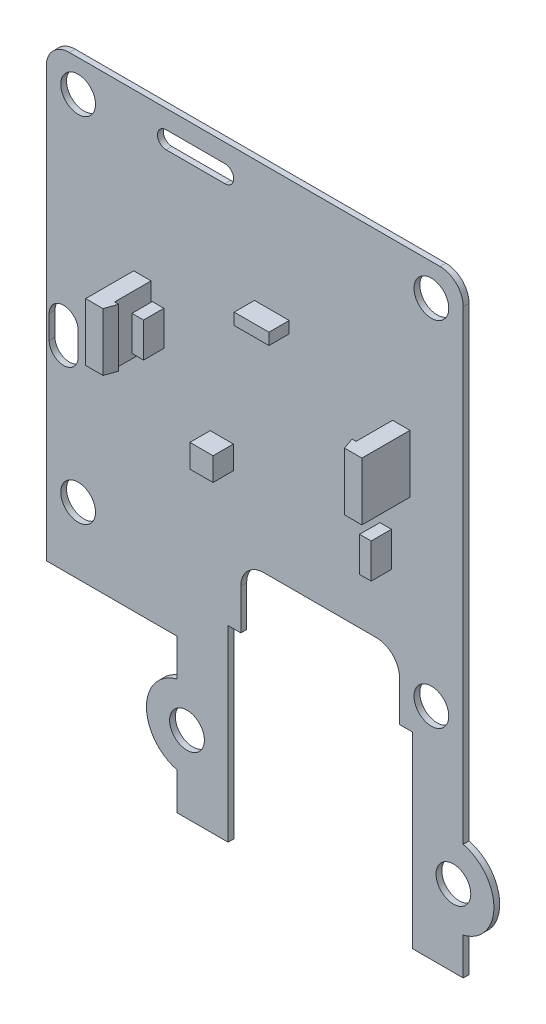
SolidWorks part; units mm, degrees
ref_plane "Front Plane" through (0, 0, 0) normal (0, 0, 1) x (1, 0, 0)
ref_plane "Top Plane" through (0, 0, 0) normal (0, 1, 0) x (1, 0, 0)
ref_plane "Right Plane" through (0, 0, 0) normal (1, 0, 0) x (0, 0, -1)
sketch "Sketch1" plane through (0, 0, 0) normal (0, 0, 1) x (1, 0, 0)
  line L0 (-17.75, -2.4) -> (-17.75, -4.4) construction
  line L1 (-15.25, -2.4) -> (-15.25, -4.4) construction
  line L2 (-17.75, -2.4) -> (-17.75, -4.4)
  line L3 (-15.25, -2.4) -> (-15.25, -4.4)
  line L4 (-7.65, 14.9) -> (-2.57, 14.9) construction
  line L5 (13.6, -18.1) -> (13.6, -34.2)
  line L6 (13.6, -34.2) -> (18, -34.2)
  line L7 (-2.3, -34.2) -> (-2.3, -18.1)
  line L8 (16, 18) -> (-16, 18)
  line L9 (-18, 16) -> (-18, -18)
  line L10 (-18, -18) -> (-1.2, -18)
  line L11 (-1.2, -18) -> (-1.2, -14.5)
  line L12 (0.8, -12.5) -> (10.5, -12.5)
  line L13 (12.5, -14.5) -> (12.5, -18)
  line L14 (12.5, -18) -> (18, -18)
  line L15 (18, -18) -> (18, 16)
  line L16 (16, 18) -> (-16, 18)
  line L17 (-18, 16) -> (-18, -18)
  line L18 (-18, -18) -> (-1.2, -18)
  line L19 (-1.2, -18) -> (-1.2, -14.5)
  line L20 (0.8, -12.5) -> (10.5, -12.5)
  line L21 (12.5, -14.5) -> (12.5, -18)
  line L22 (12.5, -18) -> (18, -18)
  line L23 (18, -18) -> (18, 16)
  line L24 (-2.3, -18.1) -> (-18, -18.1)
  line L25 (-18, -18.1) -> (-18, -21)
  line L26 (-18, -21) -> (-6.7, -21)
  line L27 (-6.7, -21) -> (-6.7, -24.2048)
  line L28 (-6.7, -30.9952) -> (-6.7, -34.2)
  line L29 (-6.7, -34.2) -> (-2.3, -34.2)
  line L30 (-2.3, -34.2) -> (-2.3, -18.1)
  line L31 (-2.3, -18.1) -> (-18, -18.1)
  line L32 (-18, -18.1) -> (-18, -21)
  line L33 (-18, -21) -> (-6.7, -21)
  line L34 (-6.7, -21) -> (-6.7, -24.2048)
  line L35 (-6.7, -30.9952) -> (-6.7, -34.2)
  line L36 (-6.7, -34.2) -> (-2.3, -34.2)
  line L37 (18, -34.2) -> (18, -30.9952)
  line L38 (18, -24.2048) -> (18, -18.1)
  line L39 (18, -18.1) -> (13.6, -18.1)
  line L40 (13.6, -18.1) -> (13.6, -34.2)
  line L41 (13.6, -34.2) -> (18, -34.2)
  line L42 (18, -34.2) -> (18, -30.9952)
  line L43 (18, -24.2048) -> (18, -18.1)
  line L44 (18, -18.1) -> (13.6, -18.1)
  line L45 (-7.65, 16.4) -> (-2.57, 16.4) construction
  line L46 (-7.65, 14.9) -> (-2.57, 14.9)
  line L47 (-7.65, 16.4) -> (-2.57, 16.4)
  line L48 (-18, -18) -> (-18, -18.1)
  line L49 (18, -18) -> (18, -18.1)
  line L50 (13.6, -18.1) -> (13.6, -18)
  line L51 (-2.3, -18.1) -> (-2.3, -18)
  arc A0 (-17.75, -4.4) -> (-15.25, -4.4) centre (-16.5, -4.4) ccw construction
  arc A1 (-6.7, -24.2048) -> (-6.7, -30.9952) centre (-5.85, -27.6) ccw
  arc A2 (-6.7, -24.2048) -> (-6.7, -30.9952) centre (-5.85, -27.6) ccw
  arc A3 (18, -30.9952) -> (18, -24.2048) centre (17.15, -27.6) ccw
  arc A4 (-16, 18) -> (-18, 16) centre (-16, 16) ccw
  arc A5 (0.8, -12.5) -> (-1.2, -14.5) centre (0.8, -14.5) ccw
  arc A6 (12.5, -14.5) -> (10.5, -12.5) centre (10.5, -14.5) ccw
  arc A7 (18, 16) -> (16, 18) centre (16, 16) ccw
  arc A8 (-16, 18) -> (-18, 16) centre (-16, 16) ccw
  arc A9 (0.8, -12.5) -> (-1.2, -14.5) centre (0.8, -14.5) ccw
  arc A10 (12.5, -14.5) -> (10.5, -12.5) centre (10.5, -14.5) ccw
  arc A11 (18, 16) -> (16, 18) centre (16, 16) ccw
  arc A12 (18, -30.9952) -> (18, -24.2048) centre (17.15, -27.6) ccw
  arc A13 (-15.25, -2.4) -> (-17.75, -2.4) centre (-16.5, -2.4) ccw construction
  arc A14 (-17.75, -4.4) -> (-15.25, -4.4) centre (-16.5, -4.4) ccw
  arc A15 (-15.25, -2.4) -> (-17.75, -2.4) centre (-16.5, -2.4) ccw
  circle A16 centre (15.25, 15.25) radius 1.5 construction
  circle A17 centre (15.25, -15.25) radius 1.5 construction
  circle A18 centre (17.15, -27.6) radius 1.5 construction
  circle A19 centre (-5.85, -27.6) radius 1.5 construction
  circle A20 centre (-15.25, -15.25) radius 1.5 construction
  circle A21 centre (-15.25, 15.25) radius 1.5 construction
  circle A22 centre (15.25, 15.25) radius 1.5
  circle A23 centre (15.25, -15.25) radius 1.5
  circle A24 centre (17.15, -27.6) radius 1.5
  circle A25 centre (-5.85, -27.6) radius 1.5
  circle A26 centre (-15.25, -15.25) radius 1.5
  circle A27 centre (-15.25, 15.25) radius 1.5
  arc A28 (-2.57, 14.9) -> (-2.57, 16.4) centre (-2.57, 15.65) ccw construction
  arc A29 (-7.65, 16.4) -> (-7.65, 14.9) centre (-7.65, 15.65) ccw construction
  arc A30 (-2.57, 14.9) -> (-2.57, 16.4) centre (-2.57, 15.65) ccw
  arc A31 (-7.65, 16.4) -> (-7.65, 14.9) centre (-7.65, 15.65) ccw
  dimension "D1" = 0
  dimension "D2" = 0
  dimension "D3" = 0
extrude "Base shape" add sketch "Sketch1" along normal blind 0.5 contours L23 A11 L16 A8 L17 L18 L19 A9 L20 A10 L21 L22 A31 L47 A30 L46 A27 A26 A23 A22 A15 L3 A14 L2 | L31 L51 L18 L48 | L34 A2 L35 L36 L30 L31 L32 L33 A25 | L50 L44 L49 L22 | L42 A12 L43 L44 L40 L41 A24 region at (16.2483, -26.2681, 0) region at (15.8, -18.05, 0) region at (-0.1744, 0.8384, 0) region at (-10.15, -18.05, 0) region at (-10.15, -18.3249, 0)
sketch "Sketch2" plane through (0, 0, 0.5) normal (0, 0, 1) x (1, 0, 0)
  line L0 (1.475, 16.95) -> (1.475, -13.05) construction
  line L1 (-7.85, 1.45) -> (-8.85, 1.45) construction
  line L2 (-0.025, 7.45) -> (2.975, 7.45)
  line L3 (-0.025, 7.45) -> (-0.025, 6.45)
  line L4 (11.8, 16.95) -> (-8.85, 16.95)
  line L5 (-8.85, 16.95) -> (-8.85, -13.05)
  line L6 (-8.85, -13.05) -> (11.8, -13.05)
  line L7 (11.8, -13.05) -> (11.8, 16.95)
  line L8 (11.8, 16.95) -> (-8.85, 16.95)
  line L9 (-8.85, 16.95) -> (-8.85, -13.05)
  line L10 (-8.85, -13.05) -> (11.8, -13.05)
  line L11 (11.8, -13.05) -> (11.8, 16.95)
  line L12 (-0.025, 6.45) -> (2.975, 6.45)
  line L13 (2.975, 7.45) -> (2.975, 6.45)
  line L14 (-0.025, 7.45) -> (2.975, 6.45) construction
  line L15 (-0.025, 6.45) -> (2.975, 7.45) construction
  line L16 (-8.85, 2.95) -> (-7.85, 2.95)
  line L17 (-8.85, 2.95) -> (-8.85, -0.05)
  line L18 (-8.85, -0.05) -> (-7.85, -0.05)
  line L19 (-7.85, 2.95) -> (-7.85, -0.05)
  line L20 (-3.85, -4.2) -> (-1.85, -4.2)
  line L21 (-3.85, -4.2) -> (-3.85, -6.2)
  line L22 (-3.85, -6.2) -> (-1.85, -6.2)
  line L23 (-1.85, -4.2) -> (-1.85, -6.2)
  line L24 (11.8, -3.75) -> (10.8, -3.75)
  line L25 (11.8, -3.75) -> (11.8, -6.75)
  line L26 (11.8, -6.75) -> (10.8, -6.75)
  line L27 (10.8, -3.75) -> (10.8, -6.75)
  line L28 (11.8, 1.95) -> (10.8, 1.95)
  line L29 (11.8, 1.95) -> (11.8, -1.05)
  line L30 (11.8, -1.05) -> (10.8, -1.05)
  line L31 (10.8, 1.95) -> (10.8, -1.05)
  line L32 (-3.85, -5.2) -> (-1.85, -5.2) construction
  line L33 (-2.85, -4.2) -> (-2.85, -6.2) construction
  line L34 (10.8, 0.45) -> (11.8, 0.45) construction
  line L35 (10.8, -5.25) -> (11.8, -5.25) construction
  point P6 (1.475, 6.95)
  dimension "D2" = 3
  dimension "D3" = 1
  dimension "D4" = 10
  dimension "D5" = 7.8
  dimension "D6" = 16.5
  dimension "D7" = 7.85
  dimension "D8" = 6
  dimension "D9" = 2
  dimension "D10" = 15.5
  dimension "D1" = 0
extrude "RX supports" add sketch "Sketch2" along normal blind 1.75 contours L13 L2 L3 L12 | L19 L16 L9 L18 | L23 L20 L21 L22 | L28 L31 L30 L11 | L24 L27 L26 L11 region at (1.475, 6.95, 0.5) region at (11.3, 0.45, 0.5) region at (-8.35, 1.45, 0.5) region at (11.3, -5.25, 0.5) region at (-2.85, -5.2, 0.5)
sketch "Sketch3" plane through (0, 0, 0.5) normal (0, 0, 1) x (1, 0, 0)
  line L0 (-8.85, 1.95) -> (11.8, 1.95) construction
  line L1 (1.475, 16.95) -> (1.475, -13.05) construction
  line L2 (-8.95, 4.45) -> (-10.45, 4.45)
  line L3 (-8.95, 4.45) -> (-8.95, -0.55)
  line L4 (11.8, 16.95) -> (-8.85, 16.95)
  line L5 (-8.85, 16.95) -> (-8.85, -13.05)
  line L6 (-8.85, -13.05) -> (11.8, -13.05)
  line L7 (11.8, -13.05) -> (11.8, 16.95)
  line L8 (11.8, 16.95) -> (-8.85, 16.95)
  line L9 (-8.85, 16.95) -> (-8.85, -13.05)
  line L10 (-8.85, -13.05) -> (11.8, -13.05)
  line L11 (11.8, -13.05) -> (11.8, 16.95)
  line L12 (-8.95, -0.55) -> (-10.45, -0.55)
  line L13 (-10.45, 4.45) -> (-10.45, -0.55)
  line L14 (11.9, -0.55) -> (13.4, -0.55)
  line L15 (13.4, 4.45) -> (13.4, -0.55)
  line L16 (11.9, 4.45) -> (13.4, 4.45)
  line L17 (11.9, 4.45) -> (11.9, -0.55)
  point P10 (-10.45, 1.95)
  point P13 (0, 0)
  point P14 (0, 0)
  point P15 (-9.1855, 4.45)
  dimension "D2" = 5
  dimension "D3" = 1.5
  dimension "D4" = 0.1
  dimension "D1" = 0
extrude "Clip base" add sketch "Sketch3" along normal offset from surface (3.15 mm away) 0.2 contours L2 L13 L12 L3 | L16 L17 L14 L15 region at (-9.7, 1.95, 0.5) region at (12.65, 1.95, 0.5) offset beyond the face yes
sketch "Sketch4" plane through (0, 0, 3.65) normal (0, 0, 1) x (1, 0, 0)
  line L0 (-8.95, -0.55) -> (-10.45, -0.55) construction
  line L1 (-10.45, 4.45) -> (-8.6, 4.45)
  line L2 (-10.45, 4.45) -> (-10.45, -0.55)
  line L3 (-10.45, -0.55) -> (-8.6, -0.55)
  line L4 (-8.6, 4.45) -> (-8.6, -0.55)
  line L5 (-8.95, 4.45) -> (-8.95, -0.55) construction
  line L6 (-10.45, 1.95) -> (13.4, 1.95) construction
  line L7 (13.4, 4.45) -> (13.4, -0.55) construction
  line L8 (1.475, 4.45) -> (1.475, -0.55) construction
  line L9 (11.55, 4.45) -> (11.55, -0.55)
  line L10 (13.4, 4.45) -> (11.55, 4.45)
  line L11 (13.4, 4.45) -> (13.4, -0.55)
  line L12 (13.4, -0.55) -> (11.55, -0.55)
  point P15 (0, 0)
  point P16 (0, 0)
  point P17 (1.475, 1.95)
  dimension "D1" = 0.35
extrude "Clip top" add sketch "Sketch4" along normal blind 1
sketch "Sketch5" plane through (0, -0.55, 0) normal (0, -1, 0) x (1, 0, 0)
  line L0 (-8.6, 3.65) -> (-8.95, 4.65)
  line L1 (-10.45, 4.65) -> (-8.6, 4.65) construction
  line L2 (-8.95, 4.65) -> (-8.6, 4.65)
  line L3 (-8.6, 4.65) -> (-8.6, 3.65)
  line L4 (-8.95, 3.65) -> (-8.95, 0.5) construction
  line L5 (11.55, 3.65) -> (11.9, 4.65)
  line L6 (11.55, 4.65) -> (13.4, 4.65) construction
  line L7 (11.9, 4.65) -> (11.55, 4.65)
  line L8 (11.55, 4.65) -> (11.55, 3.65)
  line L9 (11.9, 3.65) -> (11.9, 0.5) construction
  point P5 (0, 0)
extrude "Clip chamfer" cut sketch "Sketch5" against normal up to next
